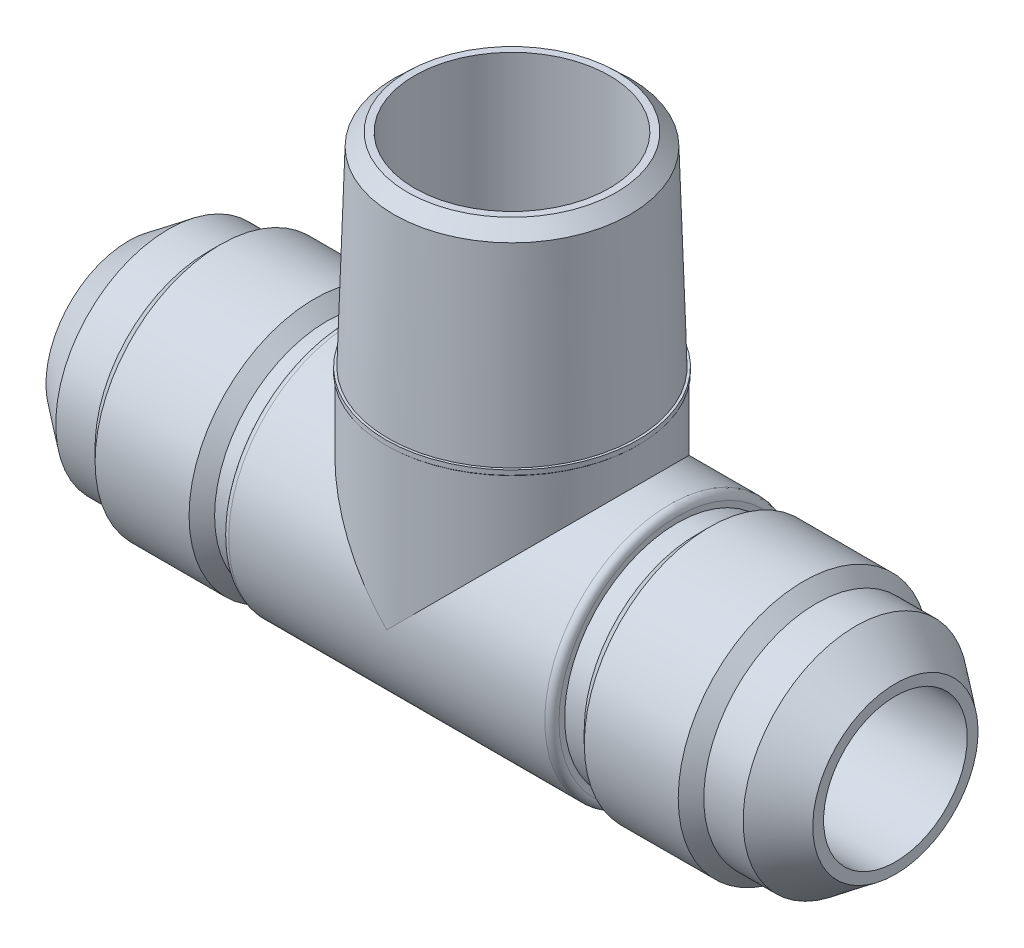
SolidWorks part; units mm, degrees
ref_plane "Front Plane" through (0, 0, 0) normal (0, 0, 1) x (1, 0, 0)
ref_plane "Top Plane" through (0, 0, 0) normal (0, 1, 0) x (1, 0, 0)
ref_plane "Right Plane" through (0, 0, 0) normal (1, 0, 0) x (0, 0, -1)
sketch "Sketch1" plane through (0, 0, 0) normal (0, 0, 1) x (1, 0, 0)
  line L0 (0, 0) -> (-17.78, 0) construction
  line L1 (0, 0) -> (0, 17.78) construction
  line L2 (-13.4937, 17.78) -> (13.4937, 17.78) construction
  line L3 (-17.78, 13.4937) -> (-17.78, -13.4937) construction
  line L6 (-41.275, 13.4937) -> (-41.275, -13.4938) construction
  line L8 (-13.335, 39.6875) -> (13.335, 39.6875) construction
  line L9 (0, 0) -> (0, 39.6875) construction
  line L10 (-17.78, 13.4874) -> (-17.78, -13.4874) construction
  line L12 (-13.4874, 17.78) -> (13.4874, 17.78) construction
  point P15 (0, 25.8267)
  dimension "S" = 23.495
  dimension "Pipe Thread Dia" = 26.67
  dimension "V" = 39.6875
  dimension "TE" = 13.8608
  dimension "OA" = 26.9748
ref_plane "Plane1" through (-41.275, 0, 0) normal (1, 0, 0) x (0, 0, -1)
sketch "Sketch2" plane through (-41.275, 0, 0) normal (1, 0, 0) x (0, 0, -1)
  circle A0 centre (0, 0) radius 13.4938
  dimension "Thread OD" = 26.9875
extrude "Extrude1" add sketch "Sketch2" along normal up to vertex (23.495 mm away) up to point (-17.78, 0, 0)
sketch "Sketch3" plane through (-41.275, 0, 0) normal (-1, 0, 0) x (0, 0, 1)
  circle A0 centre (0, 0) radius 13.4937 construction
  circle A1 centre (0, 0) radius 13.4938
curve "Helix/Spiral1" pitch 2.1167 height 41.275 turns 19.5 parameters "pitch"=2.1167
sketch "Sketch4" plane through (0, 0, 0) normal (0, 0, 1) x (1, 0, 0)
  line L0 (-43.1271, 13.4937) -> (-42.3333, 12.1189)
  line L1 (-42.3333, 12.1189) -> (-42.0687, 12.1189)
  line L2 (-42.0687, 12.1189) -> (-41.275, 13.4937)
  line L3 (-43.1271, 13.4937) -> (-41.275, 13.4937)
  line L6 (-42.201, 13.4937) -> (-42.201, 12.1189) construction
  line L7 (-42.7302, 12.8063) -> (-41.6719, 12.8063) construction
  line L8 (-41.275, 13.4937) -> (-41.275, -13.4937) construction
  dimension "D1" = 0.2646
  dimension "D2" = 1.0583
  dimension "D3" = 60
sweep "Cut-Sweep1" [suppressed] cut profiles "Sketch4" path "Helix/Spiral1"
sketch "Sketch5" plane through (0, 0, 0) normal (0, 0, 1) x (1, 0, 0)
  line L0 (-41.275, 9.525) -> (-41.275, -9.525) construction
  line L1 (-36.996, 12.1189) -> (-32.7626, 12.1189)
  line L2 (-32.7626, 12.1189) -> (-31.3878, 13.4937)
  line L3 (-41.275, 8.8944) -> (-41.275, -8.8944) construction
  line L4 (-31.3878, 13.4937) -> (-41.275, 13.4937)
  line L5 (-43.1271, 13.4937) -> (-41.275, 13.4937) construction
  line L6 (-17.78, 13.4937) -> (-17.78, -13.4937) construction
  line L7 (-17.78, 12.1189) -> (-19.8967, 12.1189)
  line L8 (-19.8967, 12.1189) -> (-21.2715, 13.4937)
  line L9 (-21.2715, 13.4937) -> (-17.78, 13.4937)
  line L10 (-17.78, 12.1189) -> (-17.78, 13.4937)
  line L11 (-29.5876, -13.4937) -> (-29.5876, 0) construction
  line L12 (-17.78, 0) -> (-41.275, 0) construction
  line L13 (-41.275, 13.4937) -> (-41.275, -13.4938) construction
  line L14 (-41.275, 8.8944) -> (-36.996, 12.1189)
  line L15 (-41.275, 13.4937) -> (-41.275, 8.8944)
  line L16 (0, 0) -> (-17.78, 0) construction
  point P16 (-29.5876, -13.4937)
  dimension "D3" = 45
  dimension "D5" = 45
  dimension "D6" = 2.1167
  dimension "Tube OD" = 19.05
  dimension "D2" = 17.7889
  dimension "D1" = 37
  dimension "D4" = 4.2333
  dimension "D7" = 3.175
revolve "Cut-Revolve1" cut sketch "Sketch5" angle 360 about L0
ref_plane "Plane2" through (-17.78, 0, 0) normal (1, 0, 0) x (0, 0, -1)
sketch "Sketch15" plane through (-17.78, 0, 0) normal (1, 0, 0) x (0, 0, -1)
  circle A0 centre (0, 0) radius 13.4874
extrude "Boss-Extrude1" add sketch "Sketch15" along normal up to vertex (17.78 mm away) up to point (0, 0, 0)
sketch "Sketch16" plane through (0, 0, 0) normal (1, 0, 0) x (0, 0, -1)
  circle A0 centre (0, 0) radius 7.7343
  dimension "Min ID" = 15.4686
extrude "Cut-Extrude1" cut sketch "Sketch16" against normal through all
ref_plane "Plane3" through (0, 17.78, 0) normal (0, 1, 0) x (-1, 0, 0)
sketch "Sketch20" plane through (0, 17.78, 0) normal (0, 1, 0) x (-1, 0, 0)
  circle A0 centre (0, 0) radius 13.4874
extrude "Boss-Extrude2" add sketch "Sketch20" against normal up to vertex (17.78 mm away) separate body up to point (0, 0, 0)
sketch "Sketch22" plane through (0, 17.78, 0) normal (0, 1, 0) x (-1, 0, 0)
  circle A0 centre (0, 0) radius 13.335
extrude "Boss-Extrude3" add sketch "Sketch22" along normal up to vertex (21.9075 mm away) draft 1.75 separate body up to point (0, 39.6875, 0)
sketch "Sketch23" plane through (0, 39.6875, 0) normal (0, 1, 0) x (1, 0, 0)
  circle A0 centre (0, 0) radius 12.6657 construction
  circle A1 centre (0, 0) radius 12.6657
curve "Helix/Spiral2" parameters "Pitch"=1.8143
chamfer "Chamfer1" distance 1.3607 angle 45 1 edges at (0, 39.6875, 12.6657) first distance on face at (0, 39.6875, 12.6657)
sketch "Sketch25" plane through (0, 17.78, 0) normal (0, -1, 0) x (1, 0, 0)
  circle A1 centre (0, 0) radius 13.335
  circle A2 centre (0, 0) radius 13.335
  dimension "D1" = 0
sketch "Sketch24" plane through (0, 0, 0) normal (0, 0, 1) x (1, 0, 0)
  line L0 (12.7639, 41.4451) -> (12.7639, 39.6308) construction
  line L1 (12.7639, 39.6308) -> (11.1926, 40.5379) construction
  line L2 (11.1926, 40.5379) -> (12.7639, 41.4451) construction
  line L3 (11.3891, 40.6513) -> (11.3891, 40.4246)
  line L4 (11.1926, 40.5379) -> (11.3891, 40.5379) construction
  line L5 (12.5675, 41.3317) -> (12.5675, 39.7442) construction
  line L6 (12.5675, 40.5379) -> (12.7639, 40.5379) construction
  line L7 (12.6657, 40.5379) -> (12.6657, 39.6875) construction
  line L8 (12.6657, 41.3884) -> (12.7639, 39.6308)
  line L9 (12.7639, 39.6308) -> (11.3891, 40.4246)
  line L10 (11.3891, 40.6513) -> (12.6657, 41.3884)
  dimension "D1" = 1.8143
  dimension "D2" = 0.2268
sweep "Cut-Sweep2" [suppressed] cut profiles "Sketch24" path "Helix/Spiral2"
extrude "Boss-Extrude4" add sketch "Sketch25" against normal up to vertex (21.9075 mm away) draft 15 up to point (13.335, 39.6875, 0)
sketch "Sketch28" plane through (0, 39.6875, 0) normal (0, 1, 0) x (1, 0, 0)
  circle A2 centre (0, 0) radius 10.4994
  circle A3 centre (0, 0) radius 10.4994
  dimension "D1" = 0.762
extrude "Cut-Extrude6" cut sketch "Sketch28" against normal up to vertex (21.9075 mm away) up to point (0, 17.78, 0)
fillet "Fillet1" radius 0.762 1 edges at (-17.78, 0, -13.4874)
sketch "Sketch10" plane through (0, 0, 0) normal (1, 0, 0) x (0, 0, -1)
  line L0 (0, 0) -> (-12.651, 0) construction
ref_axis "Axis1" through (0, 0, 12.651) along (0, 0, -1)
pattern_circular "CirPattern1" count 2 over 180 about axis through (0, 0, 12.651) along (0, 0, -1) reverse direction yes of bodies 110 103
combine bodies "Combine2" operation type add bodies to combine 110 122 114 105
sketch "Sketch30" plane through (0, 0, 0) normal (0, 0, 1) x (1, 0, 0)
  line L0 (0, 17.78) -> (0, 8.89)
  line L1 (0, 17.78) -> (-13.589, 17.78)
  line L2 (0, 0) -> (0, 17.78) construction
  line L3 (-13.589, 17.78) -> (0, 8.89) construction
  line L4 (-6.7945, 13.335) -> (-7.3507, 12.4848) construction
  line L5 (-13.589, 17.78) -> (-13.589, 17.272)
  arc A0 (-13.589, 17.272) -> (0, 8.89) centre (13.9121, 46.6508) ccw
  point P2 (0, 8.89)
  dimension "D1" = 0.254
  dimension "D2" = 1.016
  dimension "D3" = 0.508
revolve "Revolve1" add sketch "Sketch30" angle 360 about L0
sketch "Sketch26" plane through (-41.275, 0, 0) normal (-1, 0, 0) x (0, 0, 1)
  circle A0 centre (0, 0) radius 7.7343 construction
  circle A1 centre (0, 0) radius 7.7343
extrude "Cut-Extrude4" cut sketch "Sketch26" against normal through all
sketch "Sketch29" plane through (0, 0, 0) normal (0, 1, 0) x (1, 0, 0)
  circle A0 centre (0, 0) radius 7.7343
  dimension "D1" = 15.4686
extrude "Cut-Extrude7" cut sketch "Sketch29" along normal through all
sketch "Sketch12" plane through (0, 0, 0) normal (0, 0, 1) x (1, 0, 0)
  line L0 (0, 0) -> (0, 39.6875) construction
  line L2 (0, 0) -> (-41.275, 0) construction
  line L3 (10.4994, 39.6875) -> (-10.4994, 39.6875) construction
sketch "Sketch13" plane through (0, 0, 0) normal (1, 0, 0) x (0, 0, -1)
  line L0 (13.4937, 17.78) -> (-13.4937, 17.78)
  line L1 (0, 0) -> (0, 17.78) construction
  line L3 (13.4937, 0) -> (-13.4937, 0)
  circle A0 centre (0, 0) radius 7.7343
  circle A1 centre (0, 0) radius 7.7343 construction
  dimension "D1" = 26.9875
other "CPoint1" parameters "Diameter"=19.05, "StubLength"=50.8
ref_axis "Axis2" through (-51.275, 0, 0) along (1, 0, 0)
other "CPoint2" parameters "Diameter"=19.05, "StubLength"=28.575
ref_axis "Axis3" through (51.275, 0, 0) along (-1, 0, 0)
equation "\"D1@Sketch1\" = \"Thread OD@Sketch2\""
equation "\"D3@Helix/Spiral1\" = \"Q@Sketch1\""
equation "\"D1@Sketch4\" = \"pitch@Helix/Spiral1\"*.125"
equation "\"D2@Sketch4\" = \"pitch@Helix/Spiral1\"*.5"
equation "\"D6@Sketch5\" = \"pitch@Helix/Spiral1\"*1"
equation "\"D4@Sketch5\" = \"pitch@Helix/Spiral1\"*2"
equation "\"D1@Sketch13\" = \"D1@Sketch1\""
equation "\"D7@Sketch5\" = \"pitch@Helix/Spiral1\"*1.5"
equation "\"D2@Sketch5\" = \"Min ID@Sketch16\"*1.15"
equation "\"D1@Sketch24\" = \"Pitch@Helix/Spiral2\""
equation "\"D2@Sketch24\" = \"Pitch@Helix/Spiral2\"/8"
equation "\"D1@Chamfer1\" = \"Pitch@Helix/Spiral2\"*.750"
equation "\"D1@Sketch29\" =  \"Min ID@Sketch16\""
